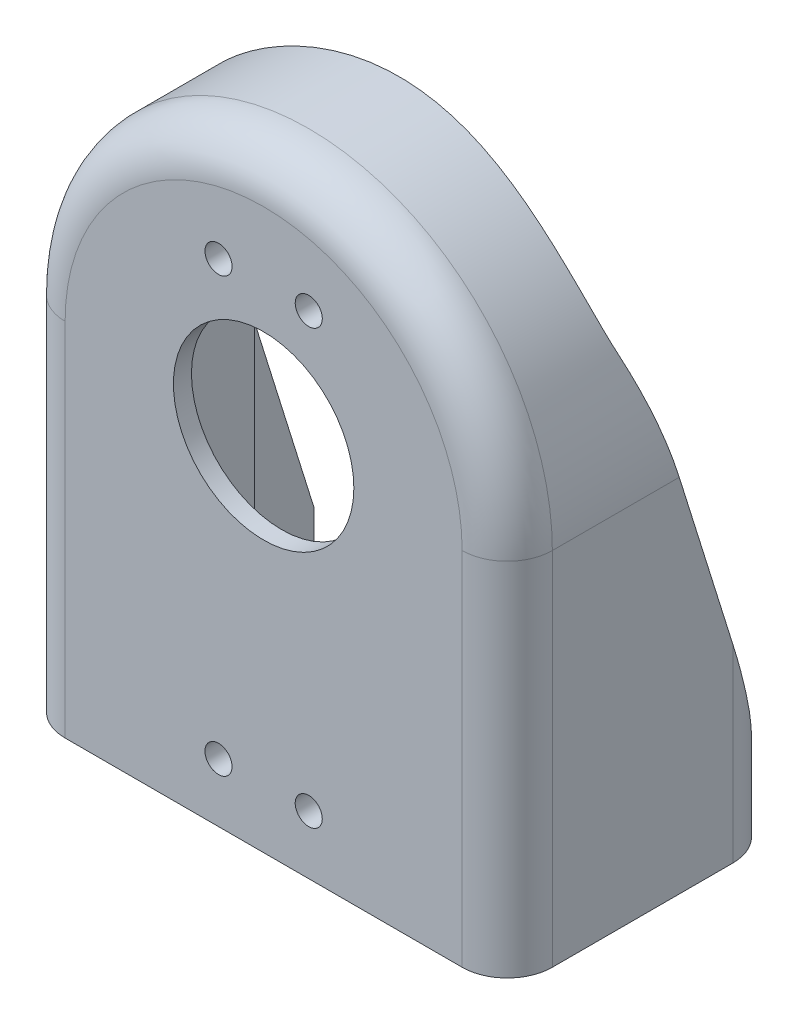
SolidWorks part; units mm, degrees
material "ABS"
ref_plane "Front Plane" through (0, 0, 0) normal (0, 0, 1) x (1, 0, 0)
ref_plane "Top Plane" through (0, 0, 0) normal (0, 1, 0) x (1, 0, 0)
ref_plane "Right Plane" through (0, 0, 0) normal (1, 0, 0) x (0, 0, -1)
sketch "Sketch3" plane through (0, 0, 0) normal (0, 0, 1) x (1, 0, 0)
  line L0 (-24, -17) -> (24, -17)
  line L1 (-27, -20) -> (27, -20)
  line L2 (-27, -20) -> (-27, 20)
  line L4 (27, -20) -> (27, 20)
  line L5 (-27, -20) -> (27, 20) construction
  line L6 (-27, 20) -> (27, -20) construction
  line L7 (24, -17) -> (24, 20)
  line L8 (-24, -17) -> (-24, 20)
  arc A0 (-27, 20) -> (27, 20) centre (0, 20) cw
  circle A1 centre (0, 20) radius 10
  arc A2 (-24, 20) -> (24, 20) centre (0, 20) cw
  point P0 (0, 0)
  dimension "D2" = 54
  dimension "D3" = 27
  dimension "D4" = 20
  dimension "D1" = 40
  dimension "D5" = 3
extrude "Boss-Extrude1" add sketch "Sketch3" against normal blind 30 contours A0 L2 L1 L4 L8 A2 L7 L0 region at (-26.1395, 0, 0)
extrude "Boss-Extrude2" add sketch "Sketch3<4>" against normal blind 10 contours A2 L8 L0 L7 A1 region at (-23.2238, 1.5, 0)
sketch "Sketch3<4>" plane through (0, 0, 0) normal (0, 0, 1) x (1, 0, 0) same geometry as "Sketch3"
sketch "Sketch5" plane through (0, 0, 0) normal (1, 0, 0) x (0, 0, -1)
  line L3 (15.255, 32.1839) -> (30, -15)
  line L4 (30, -20) -> (30, 20) construction
  line L5 (0, 47) -> (0, 20) construction
  line L6 (30, 47) -> (0, 47) construction
  line L7 (15, 47) -> (30, 47)
  line L8 (30, 47) -> (30, -15)
  arc A0 (14.6901, 34.4482) -> (15, 47) centre (44.1719, 40) cw
  arc A1 (15.255, 32.1839) -> (14.6901, 34.4482) centre (34.3446, 38.1494) cw
  point P16 (15, 33)
  dimension "D2" = 14
  dimension "D4" = 30
  dimension "D5" = 20
  dimension "D1" = 5
  dimension "D3" = 15
extrude "Cut-Extrude2" cut sketch "Sketch5" against normal through all both and the other way through all
sketch "Sketch6" plane through (0, 0, -10) normal (0, 0, -1) x (-1, 0, 0)
  line L0 (-11, 10.5) -> (11, 10.5) construction
  line L1 (-11, 31) -> (11, 31)
  line L2 (-11, 31) -> (-11, -10)
  line L3 (-11, -10) -> (11, -10)
  line L4 (11, 31) -> (11, -10)
  line L5 (-11, 31) -> (11, -10) construction
  line L6 (-11, -10) -> (11, 31) construction
  circle A0 centre (-5, 34.5) radius 1.5
  circle A1 centre (5, 34.5) radius 1.5
  circle A2 centre (5, -13.5) radius 1.5
  circle A3 centre (-5, -13.5) radius 1.5
  point P4 (0, 10.5)
  point P9 (0, 20)
  circle M8 centre (0, 20) radius 10
  dimension "D4" = 3
  dimension "D1" = 41
  dimension "D2" = 22
  dimension "D3" = 11
  dimension "D5" = 3.5
  dimension "D6" = 10
  dimension "D7" = 6
extrude "Cut-Extrude3" cut sketch "Sketch6" against normal blind 8 contours L4 L1 L2 L3 M8 region at (0, 5.4229, -10)
extrude "Cut-Extrude4" cut sketch "Sketch6<3>" against normal through all contours A3 | A2 | A0 | A1
sketch "Sketch6<3>" plane through (0, 0, -10) normal (0, 0, -1) x (-1, 0, 0) same geometry as "Sketch6"
sketch "Sketch7" plane through (0, -20, 0) normal (0, -1, 0) x (1, 0, 0)
  line L0 (-27, -25) -> (-27, -30)
  line L1 (-27, -30) -> (-22, -30)
  line L2 (22, -30) -> (27, -30)
  line L3 (27, -30) -> (27, -25)
  arc A0 (22, -30) -> (27, -25) centre (22, -25) ccw
  arc A1 (-27, -25) -> (-22, -30) centre (-22, -25) ccw
  dimension "D2" = 5
extrude "Cut-Extrude5" cut sketch "Sketch7" against normal through all
sketch "Sketch8" plane through (0, -17, 0) normal (0, 1, 0) x (1, 0, 0)
  line L0 (-24, 29.5826) -> (-24, 10) construction
  line L1 (-20, 26) -> (20, 26) construction
  line L2 (-20, 26) -> (-20, 14) construction
  line L3 (-20, 14) -> (20, 14) construction
  line L4 (20, 26) -> (20, 14) construction
  line L5 (-20, 26) -> (20, 14) construction
  line L6 (-20, 14) -> (20, 26) construction
  line L7 (24, 19.0625) -> (24, 29.5826) construction
  line L8 (-24, 10) -> (24, 10) construction
  line L9 (-22, 30) -> (22, 30) construction
  circle A0 centre (-20, 26) radius 1.5
  circle A1 centre (20, 26) radius 1.5
  circle A2 centre (20, 14) radius 1.5
  circle A3 centre (-20, 14) radius 1.5
  point P4 (0, 20)
  dimension "D5" = 3
  dimension "D1" = 4
  dimension "D2" = 4
  dimension "D3" = 4
  dimension "D4" = 4
extrude "Cut-Extrude6" cut sketch "Sketch8" against normal through all
fillet "Fillet1" radius 5 3 edges at (-27, 0, 0) (0, 47, 0) (27, 0, 0)
